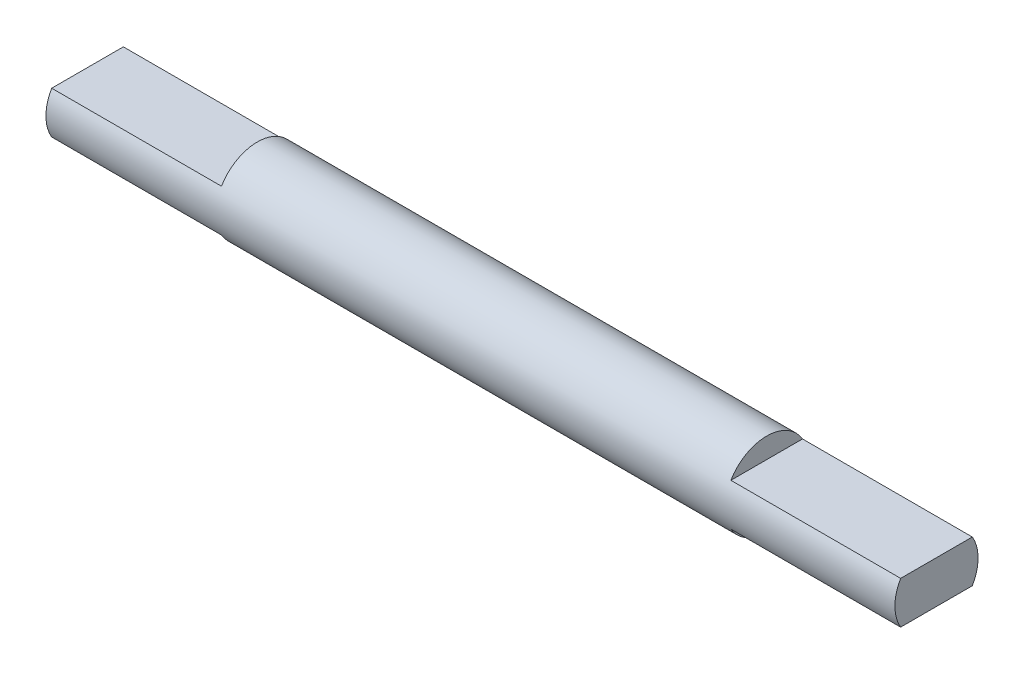
SolidWorks part; units mm, degrees
ref_plane "Front Plane" through (0, 0, 0) normal (0, 0, 1) x (1, 0, 0)
ref_plane "Top Plane" through (0, 0, 0) normal (0, 1, 0) x (1, 0, 0)
ref_plane "Right Plane" through (0, 0, 0) normal (1, 0, 0) x (0, 0, -1)
sketch "Sketch1" plane through (0, 0, 0) normal (1, 0, 0) x (0, 0, -1)
  line L0 (-2.45, 0) -> (2.45, 0) construction
  circle A0 centre (0, 0) radius 2.45
  dimension "D1" = 4.9
extrude "Boss-Extrude1" add sketch "Sketch1" along normal blind 50
sketch "Sketch2" plane through (50, 0, 0) normal (1, 0, 0) x (0, 0, -1)
  line L0 (-2.45, 0) -> (2.45, 0) construction
  line L1 (0, 1.245) -> (0, -1.245) construction
  line L2 (-2.1101, 1.245) -> (2.1101, 1.245)
  line L3 (-2.1101, -1.245) -> (2.1101, -1.245)
  arc A1 (-2.1101, 1.245) -> (2.1101, 1.245) centre (0, 0) cw
  arc A2 (-2.1101, -1.245) -> (2.1101, -1.245) centre (0, 0) ccw
  circle A3 centre (0, 0) radius 2.45 construction
  point P3 (0, 0)
  point P8 (0, 0)
  point P16 (0, -1.245)
  point P17 (0, -2.45)
  dimension "D1" = 2.49
extrude "Cut-Extrude1" cut sketch "Sketch2" against normal blind 10
extrude "Cut-Extrude2" cut sketch "Sketch2<2>" along normal blind 10 from surface starting at face at (0, 0, -2.45)
sketch "Sketch2<2>" plane through (50, 0, 0) normal (1, 0, 0) x (0, 0, -1) same geometry as "Sketch2"
